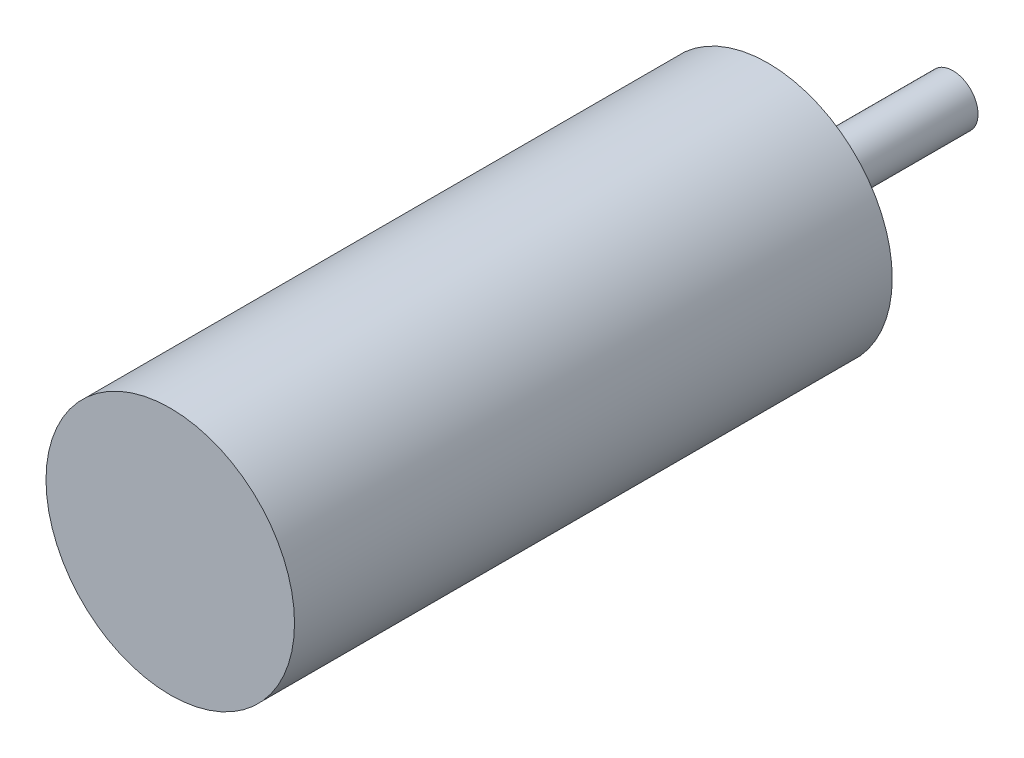
SolidWorks part; units mm, degrees
ref_plane "Front Plane" through (0, 0, 0) normal (0, 0, 1) x (1, 0, 0)
ref_plane "Top Plane" through (0, 0, 0) normal (0, 1, 0) x (1, 0, 0)
ref_plane "Right Plane" through (0, 0, 0) normal (1, 0, 0) x (0, 0, -1)
sketch "Sketch2" plane through (0, 0, 0) normal (0, 0, 1) x (1, 0, 0)
  circle A0 centre (0, 0) radius 19.75
  dimension "D1" = 39.5
extrude "Boss-Extrude1" add sketch "Sketch2" against normal blind 95
sketch "Sketch3" plane through (0, 0, -95) normal (0, 0, -1) x (-1, 0, 0)
  circle A0 centre (0, 0) radius 4
  dimension "D1" = 8
extrude "Boss-Extrude2" add sketch "Sketch3" along normal blind 29.3878
